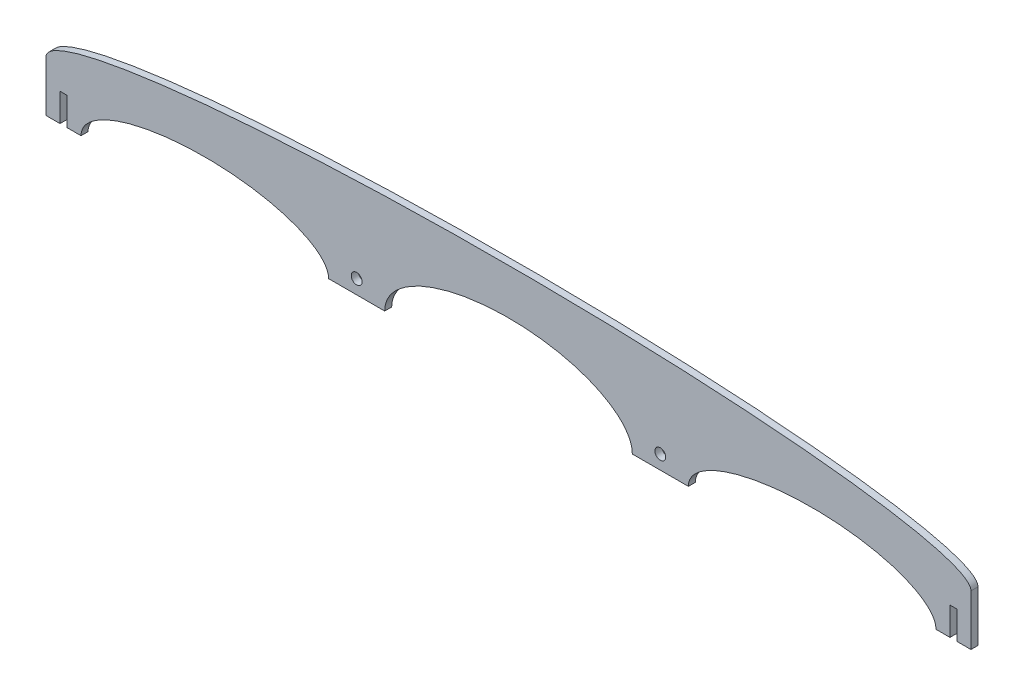
SolidWorks part; units mm, degrees
ref_plane "Front Plane" through (0, 0, 0) normal (0, 0, 1) x (1, 0, 0)
ref_plane "Top Plane" through (0, 0, 0) normal (0, 1, 0) x (1, 0, 0)
ref_plane "Right Plane" through (0, 0, 0) normal (1, 0, 0) x (0, 0, -1)
sketch "Sketch1" plane through (0, 0, 0) normal (0, 0, 1) x (1, 0, 0)
  line L0 (-209.55, 0) -> (-209.55, -23.0187)
  line L1 (209.55, 0) -> (209.55, -23.0187)
  line L2 (-209.55, -23.0187) -> (-203.2, -23.0187)
  line L3 (-203.2, -23.0187) -> (-203.2, -10.3187)
  line L4 (-203.2, -10.3187) -> (-200.025, -10.3187)
  line L5 (-200.025, -10.3187) -> (-200.025, -23.0187)
  line L6 (-200.025, -23.0187) -> (-193.675, -23.0187)
  line L7 (-81.4917, -23.0187) -> (-56.0917, -23.0187)
  line L8 (56.0917, -23.0187) -> (81.4917, -23.0187)
  line L9 (209.55, -23.0187) -> (203.2, -23.0187)
  line L10 (203.2, -23.0187) -> (203.2, -10.3187)
  line L11 (203.2, -10.3187) -> (200.025, -10.3187)
  line L12 (200.025, -10.3187) -> (200.025, -23.0187)
  line L13 (200.025, -23.0187) -> (193.675, -23.0187)
  line L14 (-193.675, -23.0187) -> (-81.4917, -23.0187) construction
  line L15 (-56.0917, -23.0187) -> (56.0917, -23.0187) construction
  line L16 (81.4917, -23.0187) -> (193.675, -23.0187) construction
  ellipse E0 centre (0, 0) end of major axis (-209.55, 0) minor radius 23.0187 (209.55, 0) -> (-209.55, 0) ccw
  ellipse E1 centre (-137.5833, -23.0187) end of major axis (-81.4917, -23.0187) minor radius 19.7436 (-81.4917, -23.0187) -> (-193.675, -23.0187) ccw
  ellipse E2 centre (0, -23.0187) end of major axis (-56.0917, -23.0187) minor radius 25.4 (56.0917, -23.0187) -> (-56.0917, -23.0187) ccw
  ellipse E3 centre (137.5833, -23.0187) end of major axis (81.4917, -23.0187) minor radius 19.7436 (193.675, -23.0187) -> (81.4917, -23.0187) ccw
  point P17 (0, 0)
  point P23 (0, 0)
  point P28 (137.5833, 17.3623)
  point P29 (0, 0)
  dimension "D1" = 46.0375
  dimension "D2" = 419.1
  dimension "D3" = 3.175
  dimension "D4" = 6.35
  dimension "D5" = 12.7
  dimension "D6" = 25.4
  dimension "D7" = 25.4
  dimension "D8" = 20.6375
extrude "Boss-Extrude1" add sketch "Sketch1" along normal blind 3.175
hole_wizard "#10 (0.1935) Diameter Hole1" positions "Sketch2" profile "Sketch3" hole size "#10" standard "ANSI Inch"
sketch "Sketch2" plane through (0, 0, 3.175) normal (0, 0, 1) x (1, 0, 0)
  line L0 (-81.4917, -23.0187) -> (-56.0917, -23.0187) construction
  line L1 (56.0917, -23.0188) -> (81.4917, -23.0187) construction
  point P0 (-68.7917, -16.6687)
  point P2 (68.7917, -16.6687)
  point P7 (-68.7917, -23.0187)
  point P10 (68.7917, -23.0187)
  dimension "D1" = 6.35
sketch "Sketch3" plane through (-68.7917, -16.6687, 3.175) normal (1, 0, 0) x (0, -1, 0)
  line L0 (0, 0) -> (0, 20.4786)
  line L1 (0, 20.4786) -> (2.4574, 19.002)
  line L2 (2.4574, 19.002) -> (2.4574, 0)
  line L5 (2.4574, 0) -> (0, 0)
  line L10 (0, 20.4786) -> (-2.4575, 19.002) construction
  line L11 (0, -6.35) -> (0, 107.95) construction
  dimension "Hole Dia." = 4.9149
  dimension "Hole Depth" = 19.002
  dimension "Drill Angle" = 118
